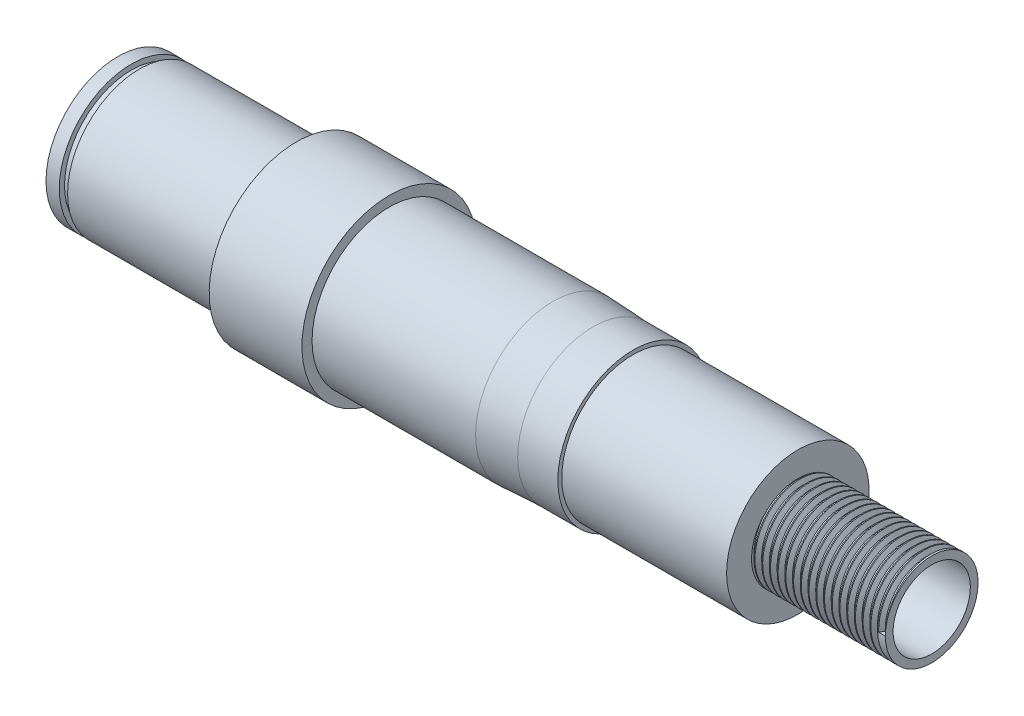
SolidWorks part; units mm, degrees
ref_plane "Front Plane" through (0, 0, 0) normal (0, 0, 1) x (1, 0, 0)
ref_plane "Top Plane" through (0, 0, 0) normal (0, 1, 0) x (1, 0, 0)
ref_plane "Right Plane" through (0, 0, 0) normal (1, 0, 0) x (0, 0, -1)
sketch "Sketch1" plane through (0, 0, 0) normal (0, 0, 1) x (1, 0, 0)
  line L0 (0, 0) -> (278.9992, 0) construction
  line L1 (84.4169, 14.986) -> (92.2084, 14.605)
  line L2 (0, 0) -> (34.6583, 0)
  line L3 (0, 0) -> (0, 13.97)
  line L4 (0, 13.97) -> (2.5781, 13.97)
  line L6 (34.6583, 0) -> (52.6669, 0)
  line L8 (34.6583, 16.9481) -> (52.6669, 16.9482)
  line L10 (52.6669, 14.986) -> (84.4169, 14.986)
  line L12 (52.6669, 0) -> (84.4169, 0)
  line L16 (84.4169, 0) -> (99.9998, 0)
  line L18 (52.6669, 16.9482) -> (52.6669, 14.986)
  line L19 (34.6583, 13.97) -> (34.6583, 16.9481)
  line L20 (99.9998, 13.843) -> (131.9998, 13.843)
  line L21 (131.9998, 13.843) -> (131.9998, 9)
  line L22 (131.9998, 0) -> (99.9998, 0)
  line L23 (4.191, 13.97) -> (34.6583, 13.97)
  line L24 (131.9998, 0) -> (157.9863, 0)
  line L26 (131.9998, 9) -> (157.9863, 9)
  line L27 (157.9863, 0) -> (157.9863, 9)
  line L29 (2.5781, 13.97) -> (2.5781, 12.954)
  line L30 (2.5781, 12.954) -> (4.191, 12.954)
  line L31 (4.191, 13.97) -> (4.191, 12.954)
  line L32 (92.2084, 14.605) -> (99.9998, 14.605)
  line L33 (99.9998, 14.605) -> (99.9998, 13.843)
  dimension "D1" = 13.97
  dimension "D2" = 34.6583
  dimension "D3" = 16.9481
  dimension "D4" = 18.0086
  dimension "D5" = 14.986
  dimension "D6" = 31.75
  dimension "D7" = 13.843
  dimension "D8" = 15.5829
  dimension "D9" = 32
  dimension "D10" = 9
  dimension "D11" = 30.4673
  dimension "D12" = 1.6129
  dimension "D13" = 1.016
  dimension "D14" = 0.762
revolve "Revolve1" add sketch "Sketch1" angle 360 about L0
thread "Thread1" pitch 1.5 method cut profile "Thread Profile1" start angle 0, offset 0, length 0, pitch 1.5, diameter 18
ref_plane "Plane1" through (157.9863, 0, 9) normal (0, -1, 0) x (0, 0, 1)
sketch "Thread Profile1" plane through (157.9863, 0, 9) normal (0, -1, 0) x (0, 0, 1)
  line L0 (0, 0) -> (0, 1.5) construction
  line L11 (0, 0) -> (0, 1.3125)
  line L12 (0, 1.3125) -> (-0.8119, 0.8437)
  line L13 (-0.8119, 0.8437) -> (-0.8119, 0.4687)
  line L15 (-0.8119, 0.4687) -> (0, 0)
  line L17 (-0.8119, 0.6562) -> (0, 0.6562) construction
  point P2 (0, 0)
  dimension "Pitch" = 1.5
  dimension "Profile_Angle" = 60
  dimension "Profile_Land" = 0.375
  dimension "Profile_Height" = 0.8119
sketch "Sketch5" plane through (157.9863, 0, 0) normal (1, 0, 0) x (0, 0, -1)
  circle A0 centre (0, 0) radius 7.5
  dimension "D1" = 15
extrude "Cut-Extrude1" cut sketch "Sketch5" against normal up to surface (105.3194 mm away) up to face at (52.6669, 0, 16.9482)
ref_plane "Plane2" through (0, -13.97, 0) normal (0, -1, 0) x (-1, 0, 0)
sketch "Sketch7" plane through (0, -13.97, 0) normal (0, -1, 0) x (-1, 0, 0)
  line L0 (-27.1183, 0) -> (-9.791, 0) construction
  line L1 (-27.1183, 3) -> (-9.791, 3)
  line L2 (-27.1183, -3) -> (-9.791, -3)
  line L3 (-34.6583, 0) -> (-4.191, 0) construction
  line L4 (-34.6583, -13.97) -> (-34.6583, 13.97) construction
  line L5 (-4.191, -12.954) -> (-4.191, 12.954) construction
  arc A0 (-27.1183, 3) -> (-27.1183, -3) centre (-27.1183, 0) ccw
  arc A1 (-9.791, -3) -> (-9.791, 3) centre (-9.791, 0) ccw
  point P2 (-18.4547, 0)
  point P7 (-6.791, 0)
  point P8 (-30.1183, 0)
  dimension "D1" = 3
  dimension "D2" = 2.6
  dimension "D3" = 4.54
extrude "Cut-Extrude3" cut sketch "Sketch7" against normal blind 3.5
sketch3d "3DSketch1"
  line L0 (27.1183, -13.6441, -3) -> (27.1183, -13.6441, 3) construction
ref_plane "Plane3" through (0.8715, 1.5095, 0) normal (-0.5, -0.866, 0) x (0, 0, 1)
sketch "Sketch8" plane through (0.8715, 1.5095, 0) normal (-0.5, -0.866, 0) x (0, 0, 1)
  circle A0 centre (0, -46.489) radius 8
  ellipse E0 centre (0, -30.015) end of major axis (16.9481, -30.015) minor radius 8.4741 construction
  point P2 (0, -40.937)
  dimension "D1" = 16
extrude "Cut-Extrude4" cut sketch "Sketch8" against normal blind 25.852 contours A0
sketch "Sketch9" plane through (52.6669, 0, 0) normal (1, 0, 0) x (0, 0, -1)
  line L0 (-23.2975, 0) -> (23.5352, 0) construction
  line L1 (-7.5, 0) -> (7.5, 0)
  arc A0 (7.5, 0) -> (-7.5, 0) centre (0, 0) ccw
revolve "Cut-Revolve1" cut sketch "Sketch9" angle 360 about L0
